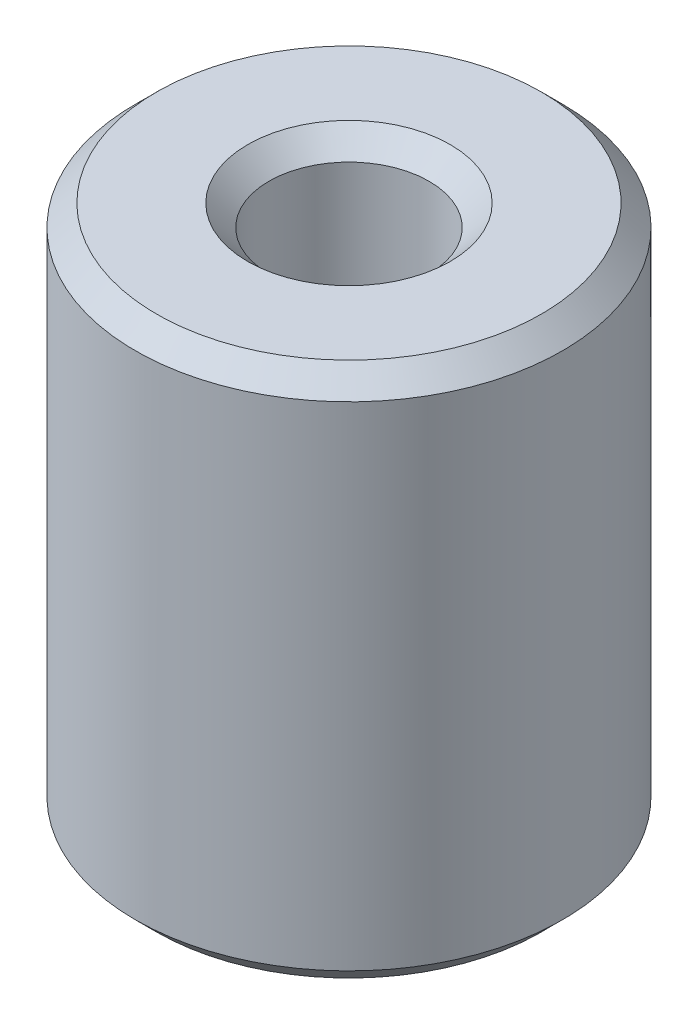
SolidWorks part; units mm, degrees
ref_plane "Front Plane" through (0, 0, 0) normal (0, 0, 1) x (1, 0, 0)
ref_plane "Top Plane" through (0, 0, 0) normal (0, 1, 0) x (1, 0, 0)
ref_plane "Right Plane" through (0, 0, 0) normal (1, 0, 0) x (0, 0, -1)
sketch "Sketch1" plane through (0, 0, 0) normal (0, 1, 0) x (1, 0, 0)
  circle A0 centre (0, 0) radius 17.5
  dimension "SLEEVE_OD" = 35
extrude "Boss-Extrude1" add sketch "Sketch1" along normal blind 43.8486
sketch "Sketch2" plane through (0, 0, 0) normal (0, 1, 0) x (1, 0, 0)
  circle A0 centre (0, 0) radius 6.564
  dimension "BORE_D" = 13.128
extrude "Cut-Extrude1" cut sketch "Sketch2" along normal through all
chamfer "Chamfer1" distance 1.7343 angle 45 4 edges at (0, 43.8486, 6.564) (0, 0, 6.564) (0, 0, 17.5) (0, 43.8486, 17.5)
